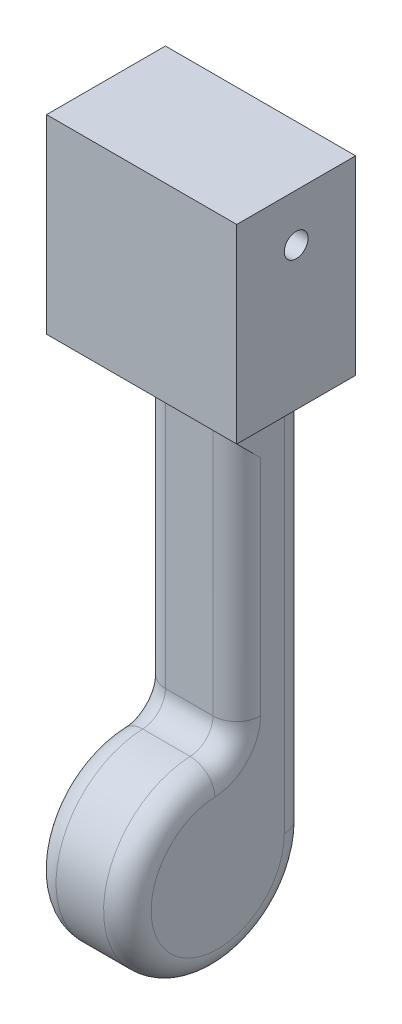
SolidWorks part; units mm, degrees
material "ABS"
ref_plane "Front Plane" through (0, 0, 0) normal (0, 0, 1) x (1, 0, 0)
ref_plane "Top Plane" through (0, 0, 0) normal (0, 1, 0) x (1, 0, 0)
ref_plane "Right Plane" through (0, 0, 0) normal (1, 0, 0) x (0, 0, -1)
sketch "Sketch1" plane through (0, 0, 0) normal (1, 0, 0) x (0, 0, -1)
  line L0 (-2.5, -124.5742) -> (-2.5, -125)
  line L1 (-12.5, -20) -> (-2.5, -20)
  line L2 (-12.5, -20) -> (-12.5, 20)
  line L3 (-12.5, 20) -> (12.5, 20)
  line L4 (12.5, -20) -> (12.5, 20)
  line L5 (-12.5, -20) -> (12.5, 20) construction
  line L6 (-12.5, 20) -> (12.5, -20) construction
  line L8 (12.5, -20) -> (12.5, -106)
  line L10 (-2.5, -20) -> (-2.5, -87.4258)
  line L11 (0, 0) -> (0, 10) construction
  line L12 (12.5, -20) -> (-2.5, -20)
  line L13 (0, 10) -> (-6.5, -106) construction
  arc A0 (-2.5, -87.4258) -> (12.5, -106) centre (-6.5, -106) ccw
  circle A1 centre (0, 10) radius 2.5
  point P0 (0, 0)
extrude "Boss-Extrude2" add sketch "Sketch1" along normal mid plane 20 contours L10 A0 L8 L12 region at (0, -81.6794, 0.7695)
extrude "Boss-Extrude3" add sketch "Sketch1<5>" along normal mid plane 40 contours L12 L4 L3 L2 L1 A1 region at (0, -0.2003, 0)
sketch "Sketch1<5>" plane through (0, 0, 0) normal (1, 0, 0) x (0, 0, -1) same geometry as "Sketch1"
chamfer "Chamfer1" distance 10 angle 45 1 edges at (0, -20, 2.5)
fillet "Fillet1" radius 5 7 edges at (-10, -58.7129, 2.5) (10, -58.7129, 2.5) (-10, -63, -12.5) (10, -63, -12.5) (-10, -117.9373, 21.2817) (10, -117.9373, 21.2817) (0, -87.4258, 2.5)
ref_axis "Axis2" through (0, 10, 0) along (1, 0, 0)
